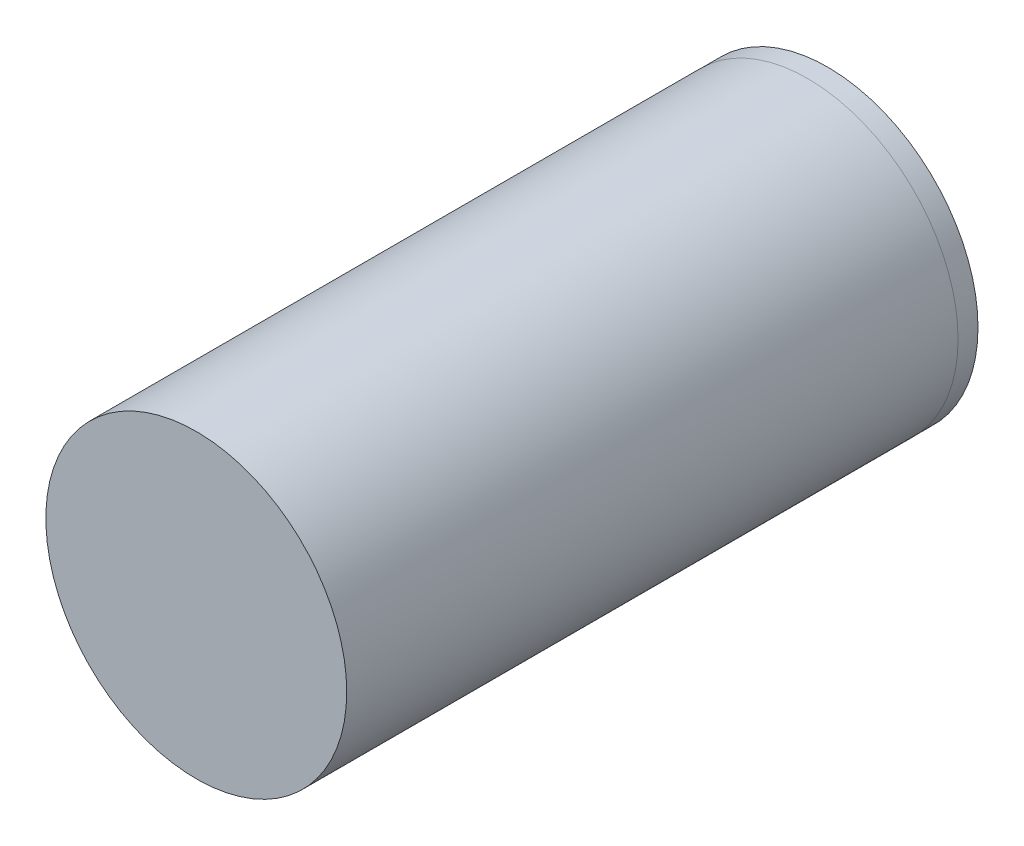
SolidWorks part; units mm, degrees
ref_plane "Front Plane" through (0, 0, 0) normal (0, 0, 1) x (1, 0, 0)
ref_plane "Top Plane" through (0, 0, 0) normal (0, 1, 0) x (1, 0, 0)
ref_plane "Right Plane" through (0, 0, 0) normal (1, 0, 0) x (0, 0, -1)
sketch "Sketch1" plane through (0, 0, 0) normal (0, 0, 1) x (1, 0, 0)
  circle A5 centre (0.7008, -0.3504) radius 5.5
  point P6 (0, 0)
  point P9 (0, 0)
  point P14 (0.7008, -1.8504)
extrude "Boss-Extrude1" add sketch "Sketch1" along normal blind 3.25 contours A5
sketch "Sketch3" plane through (0, 0, 3.25) normal (0, 0, 1) x (1, 0, 0)
  circle A0 centre (0.7008, -0.3504) radius 15
  dimension "D1" = 30
extrude "Boss-Extrude2" add sketch "Sketch3" along normal blind 2 contours A0
sketch "Sketch4" plane through (0, 0, 5.25) normal (0, 0, 1) x (1, 0, 0)
  circle A0 centre (0.7008, -0.3504) radius 15.0111
  circle A1 centre (0.7008, -0.3504) radius 13.0111
  dimension "D1" = 2
extrude "Boss-Extrude3" add sketch "Sketch4" along normal blind 59
sketch "Sketch5" plane through (0, 0, 64.25) normal (0, 0, 1) x (1, 0, 0)
  circle A0 centre (0.7008, -0.3504) radius 15.0111
extrude "Boss-Extrude4" add sketch "Sketch5" along normal blind 2
